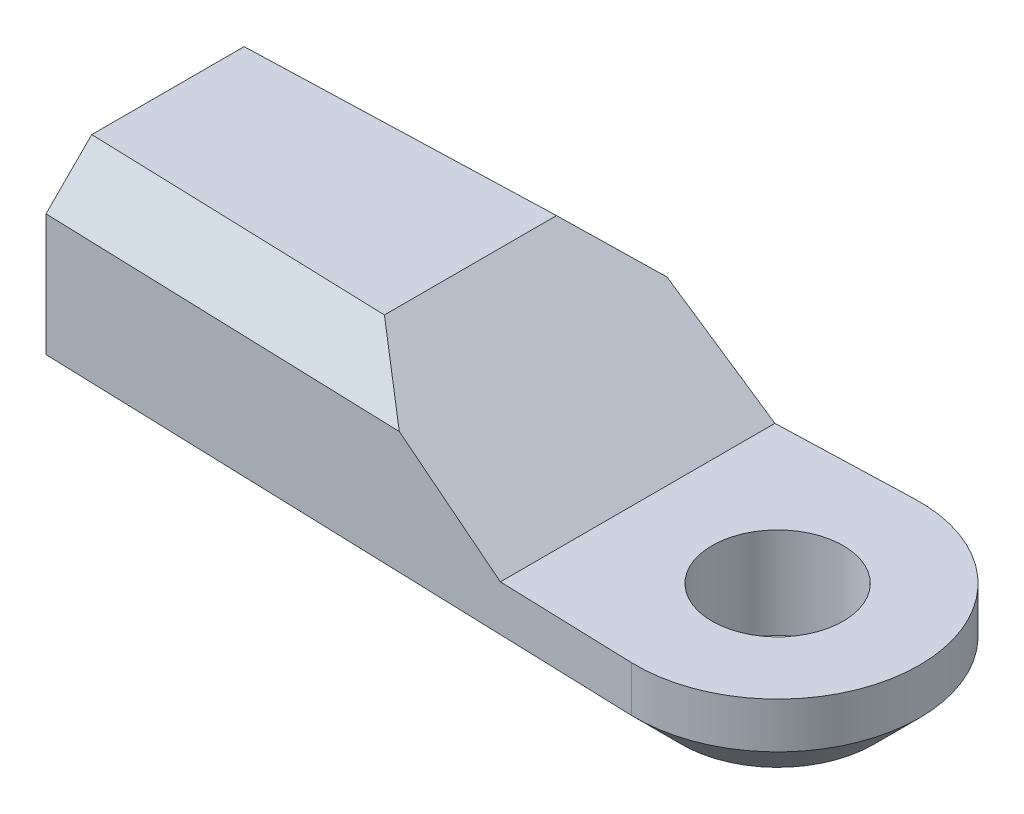
SolidWorks part; units mm, degrees
ref_plane "Front Plane" through (0, 0, 0) normal (0, 0, 1) x (1, 0, 0)
ref_plane "Top Plane" through (0, 0, 0) normal (0, 1, 0) x (1, 0, 0)
ref_plane "Right Plane" through (0, 0, 0) normal (1, 0, 0) x (0, 0, -1)
sketch "Sketch8" plane through (0, 0, 0) normal (0, 1, 0) x (1, 0, 0)
  line L0 (0, -4) -> (0, 4)
  line L1 (0, 4) -> (19.8484, 4.6475)
  line L2 (0, 0) -> (54.3416, 0) construction
  line L3 (0, -4) -> (19.8484, -4.6475)
  line L4 (0, 0) -> (10, 0) construction
  circle A0 centre (20, 0) radius 2.15
  arc A1 (19.8484, -4.6475) -> (19.8484, 4.6475) centre (20, 0) ccw
  point P3 (0, 0)
  dimension "D1" = 4.3
  dimension "D4" = 2.5
  dimension "D2" = 10
  dimension "D3" = 10
  dimension "D5" = 8
extrude "Boss-Extrude2" add sketch "Sketch8" along normal blind 7 contours A1 L0 A0 region at (11.5842, 0, 0)
sketch "Sketch9" plane through (0, 0, 0) normal (-1, 0, 0) x (0, 0, 1)
  line L0 (0, 0) -> (0, 7) construction
  line L2 (4, 7) -> (-4, 7) construction
  circle A0 centre (0, 3.5) radius 1.975
  dimension "D1" = 3.95
extrude "Cut-Extrude5" cut sketch "Sketch9" against normal blind 10
sketch "Sketch10" plane through (0, 0, 0) normal (0, 0, 1) x (1, 0, 0)
  line L0 (9.9242, 7) -> (15.408, 3)
  line L1 (0, 7) -> (19.8484, 7) construction
  line L2 (15.408, 3) -> (24.65, 3)
  line L4 (24.65, 3) -> (24.65, 7)
  line L5 (24.65, 7) -> (9.9242, 7)
  line L6 (24.65, 0) -> (24.65, 7) construction
  line L7 (0, 3.5) -> (10, 3.5) construction
  line L8 (0, 7) -> (0, 0) construction
  point P4 (17.2309, 3)
  point P6 (15.976, 3)
  point P7 (15.408, 3)
  dimension "D1" = 3
  dimension "D2" = 10
extrude "Cut-Extrude6" cut sketch "Sketch10" against normal blind 10 and the other way blind 10
chamfer "Chamfer1" distance 1.5 5 edges at (9.9242, 0, 4.3238) (24.65, 0, 0) (9.9242, 0, -4.3238) (4.9621, 7, -4.1619) (4.9621, 7, 4.1619)
